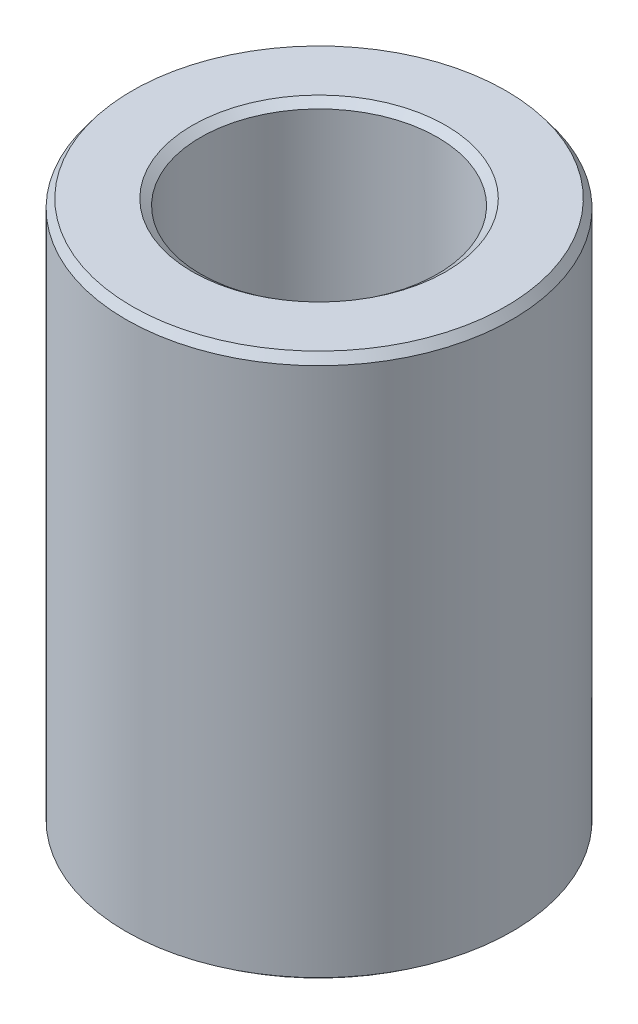
SolidWorks part; units mm, degrees
ref_plane "Front Plane" through (0, 0, 0) normal (0, 0, 1) x (1, 0, 0)
ref_plane "Top Plane" through (0, 0, 0) normal (0, 1, 0) x (1, 0, 0)
ref_plane "Right Plane" through (0, 0, 0) normal (1, 0, 0) x (0, 0, -1)
sketch "Sketch1" plane through (0, 0, 0) normal (0, 1, 0) x (1, 0, 0)
  circle A0 centre (0, 0) radius 20
  dimension "SLEEVE_OD" = 40
extrude "Boss-Extrude1" add sketch "Sketch1" along normal blind 56.4109
sketch "Sketch2" plane through (0, 0, 0) normal (0, 1, 0) x (1, 0, 0)
  circle A0 centre (0, 0) radius 12.2757
  dimension "BORE_D" = 24.5514
extrude "Cut-Extrude1" cut sketch "Sketch2" along normal through all
chamfer "Chamfer1" distance 0.8588 angle 36.639 4 edges at (0, 56.4109, 12.2757) (0, 0, 12.2757) (0, 0, 20) (0, 56.4109, 20) first distance on face at (0, 56.4109, 12.2757) first distance on face at (0, 0, 12.2757) first distance on face at (0, 56.4109, 20)
